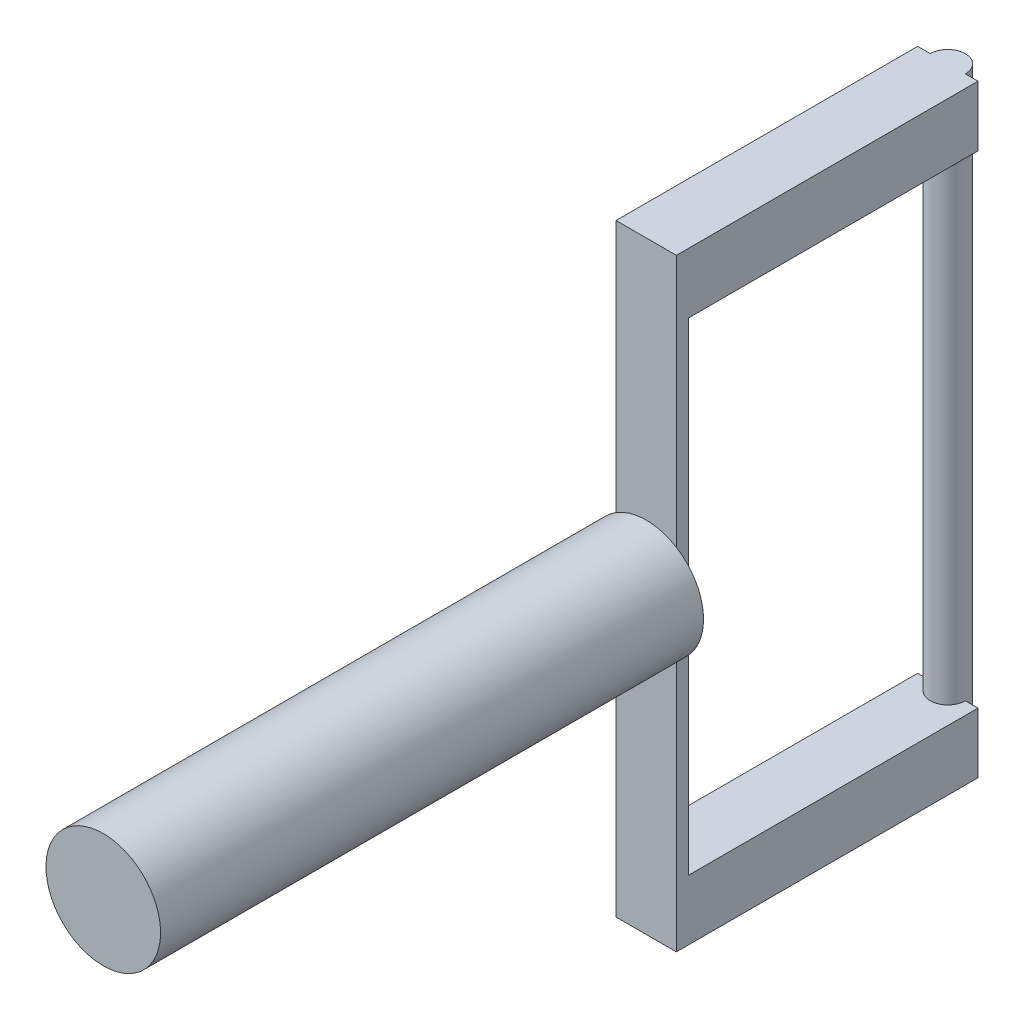
SolidWorks part; units mm, degrees
ref_plane "前视基准面" through (0, 0, 0) normal (0, 0, 1) x (1, 0, 0)
ref_plane "上视基准面" through (0, 0, 0) normal (0, 1, 0) x (1, 0, 0)
ref_plane "右视基准面" through (0, 0, 0) normal (1, 0, 0) x (0, 0, -1)
sketch "草图1" plane through (0, 0, 0) normal (0, 1, 0) x (1, 0, 0)
  circle A0 centre (0, 0) radius 0.29
  dimension "D1" = 0.58
extrude "凸台-拉伸1" add sketch "草图1" along normal mid plane 10 contours A0
sketch "草图2" plane through (0, 0, 0) normal (0, 0, 1) x (1, 0, 0)
  line L1 (-0.5, 5) -> (0.5, 5)
  line L2 (-0.5, 5) -> (-0.5, 4)
  line L3 (-0.5, 4) -> (0.5, 4)
  line L4 (0.5, 5) -> (0.5, 4)
  line L5 (-0.5, 5) -> (0.5, 4) construction
  line L6 (-0.5, 4) -> (0.5, 5) construction
  line L7 (0.5, -4) -> (-0.5, -4)
  line L8 (0.5, -4) -> (0.5, -5)
  line L9 (0.5, -5) -> (-0.5, -5)
  line L10 (-0.5, -4) -> (-0.5, -5)
  line L11 (0.5, -4) -> (-0.5, -5) construction
  line L12 (0.5, -5) -> (-0.5, -4) construction
  point P0 (0, 4.5)
  point P5 (0, -4.5)
  dimension "D1" = 4.5
  dimension "D2" = 4.5
extrude "凸台-拉伸2" add sketch "草图2" along normal blind 5
sketch "草图3" plane through (0, 0, 5) normal (0, 0, 1) x (1, 0, 0)
  line L1 (-0.5, 4) -> (0.5, 4)
  line L2 (-0.5, 4) -> (-0.5, -4)
  line L3 (-0.5, -4) -> (0.5, -4)
  line L4 (0.5, 4) -> (0.5, -4)
  line L5 (-0.5, 4) -> (0.5, -4) construction
  line L6 (-0.5, -4) -> (0.5, 4) construction
  point P0 (0, 0)
  dimension "D1" = 1
  dimension "D2" = 8
extrude "凸台-拉伸3" add sketch "草图3" against normal blind 0.2
sketch "草图4" plane through (0, 0, 5) normal (0, 0, 1) x (1, 0, 0)
  circle A0 centre (0, 0) radius 0.95
  dimension "D1" = 1.9
extrude "凸台-拉伸4" add sketch "草图4" along normal blind 9
